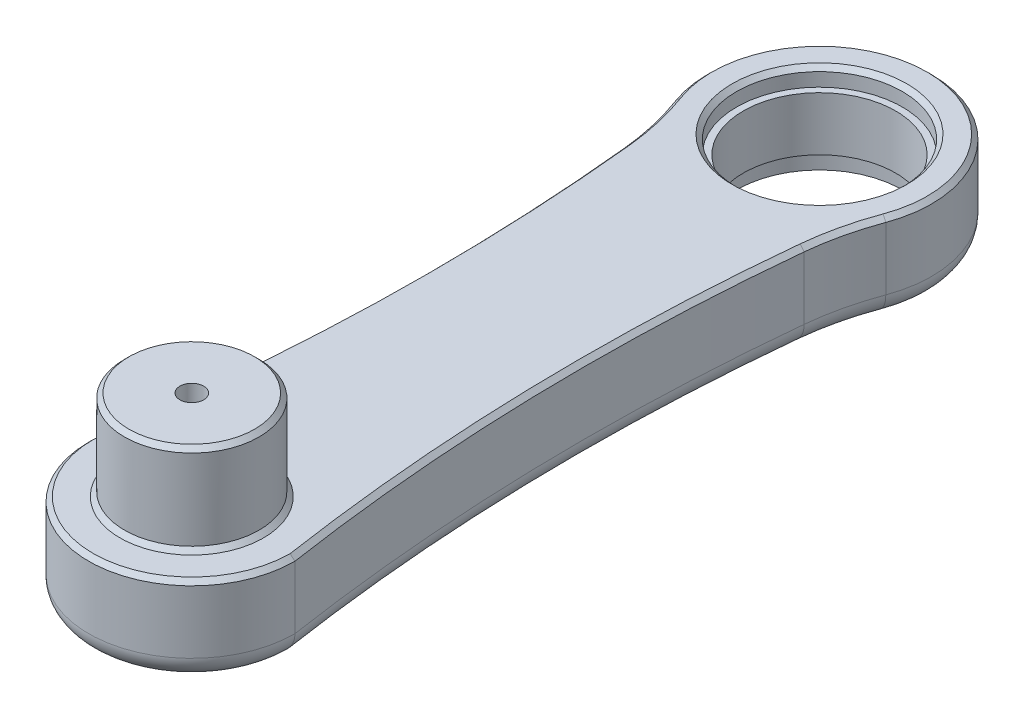
SolidWorks part; units mm, degrees
ref_plane "Front Plane" through (0, 0, 0) normal (0, 0, 1) x (1, 0, 0)
ref_plane "Top Plane" through (0, 0, 0) normal (0, 1, 0) x (1, 0, 0)
ref_plane "Right Plane" through (0, 0, 0) normal (1, 0, 0) x (0, 0, -1)
sketch "Sketch1" plane through (0, 0, 0) normal (0, 1, 0) x (1, 0, 0)
  line L0 (0, 0) -> (0, 140) construction
  line L1 (0, 71.7271) -> (35.776, 71.7271) construction
  arc A6 (-23, 0) -> (23, 0) centre (0, 0) ccw
  arc A11 (20.0339, 116.5546) -> (23, 0) centre (482.1657, 70) ccw
  arc A12 (23.4505, 131.3355) -> (-23.4505, 131.3355) centre (0, 140) ccw
  arc A13 (-20.0339, 116.5546) -> (-23, 0) centre (-482.1657, 70) cw
  arc A14 (20.0339, 116.5546) -> (23.4505, 131.3355) centre (79.7317, 110.5407) cw
  arc A15 (-23.4505, 131.3355) -> (-20.0339, 116.5546) centre (-79.7317, 110.5407) cw
  point P11 (21.1687, 126.7001)
  point P18 (-21.1687, 126.7001)
  dimension "D1" = 60
  dimension "D2" = 140
extrude "Boss-Extrude1" add sketch "Sketch1" along normal blind 20
sketch "Sketch2" plane through (0, 20, 0) normal (0, 1, 0) x (1, 0, 0)
  circle A0 centre (0, 0) radius 15.01
  dimension "D1" = 30.02
extrude "Boss-Extrude2" add sketch "Sketch2" along normal blind 20
chamfer "Chamfer1" distance 1 angle 45 1 edges at (0, 40, 15.01)
sketch "Sketch3" plane through (0, 20, 0) normal (0, 1, 0) x (1, 0, 0)
  circle A1 centre (0, 140) radius 18.485
  dimension "D1" = 36.97
extrude "Cut-Extrude1" cut sketch "Sketch3" against normal blind 20
chamfer "Chamfer3" distance 1 angle 45 8 edges at (0, 20, 23) (0, 20, -15.01) (17.8452, 20, -58.1839) (-17.8452, 20, -58.1839) (-21.2732, 20, -124.0535) (0, 20, -165) (21.2732, 20, -124.0535) (0, 20, -121.515)
sketch "Sketch5" plane through (0, 40, 0) normal (0, 1, 0) x (1, 0, 0)
  circle A0 centre (0, 0) radius 2.65
  dimension "D1" = 5.3
extrude "Cut-Extrude2" cut sketch "Sketch5" against normal blind 40
ref_plane "Plane1" through (0, 10, 0) normal (0, 1, 0) x (1, 0, 0)
fillet "Fillet3" radius 5 6 edges at (-17.8452, 0, -58.1839) (-21.2732, 0, -124.0535) (0, 0, -165) (21.2732, 0, -124.0535) (0, 0, 23) (17.8452, 0, -58.1839)
sketch "Sketch6" plane through (0, 0, 0) normal (0, -1, 0) x (1, 0, 0)
  circle A0 centre (0, 0) radius 3.65
  dimension "D1" = 7.3
extrude "Cut-Extrude3" cut sketch "Sketch6" against normal blind 8
chamfer "Chamfer4" distance 0.5 angle 45 1 edges at (0, 0, -3.65)
sketch "Sketch7" plane through (0, 10, 0) normal (0, 1, 0) x (1, 0, 0)
  circle A0 centre (0, 140) radius 18.485
  circle A1 centre (0, 140) radius 16.985
  circle A2 centre (0, 140) radius 18.485 construction
  dimension "D1" = 1.5
  dimension "D2" = 0
extrude "Boss-Extrude3" add sketch "Sketch7" along normal blind 6 and the other way blind 6
